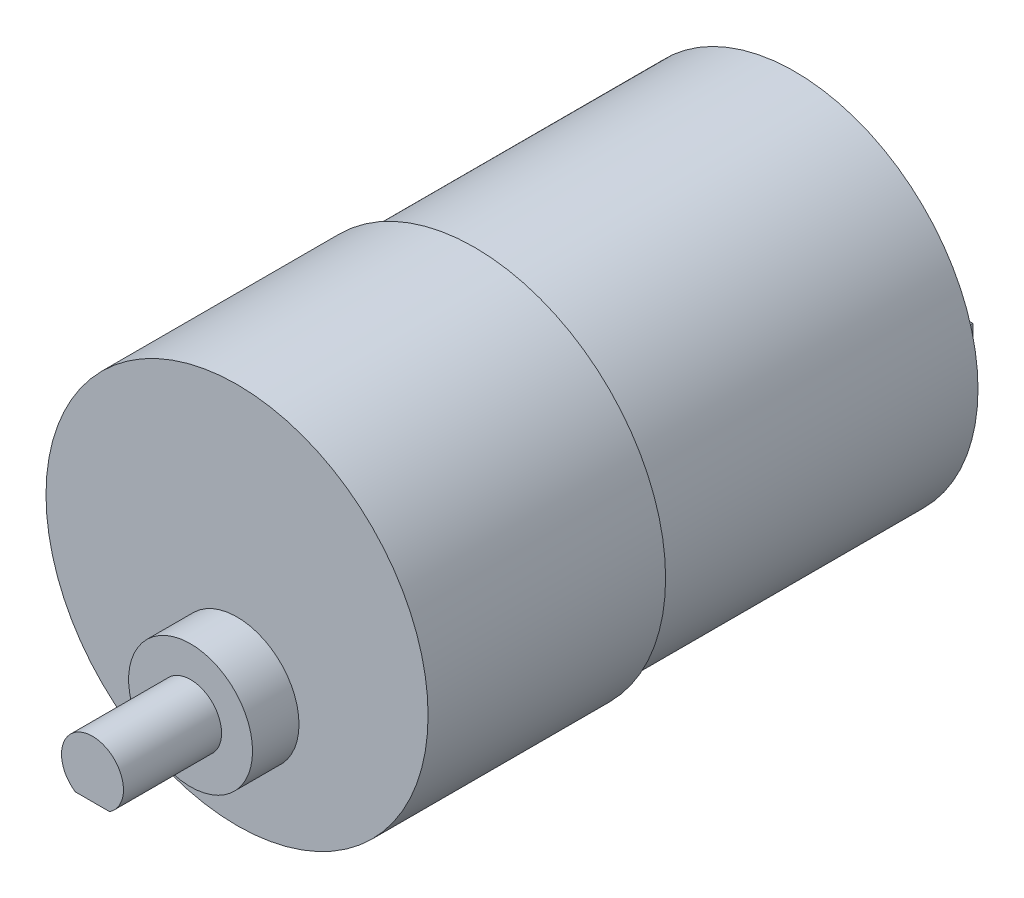
SolidWorks part; units mm, degrees
ref_plane "Front Plane" through (0, 0, 0) normal (0, 0, 1) x (1, 0, 0)
ref_plane "Top Plane" through (0, 0, 0) normal (0, 1, 0) x (1, 0, 0)
ref_plane "Right Plane" through (0, 0, 0) normal (1, 0, 0) x (0, 0, -1)
sketch "Sketch2" plane through (0, 0, 0) normal (0, 1, 0) x (1, 0, 0)
  line L0 (0, -54) -> (0, 0)
  line L1 (0, 0) -> (17.75, 0)
  line L2 (17.75, 0) -> (17.75, -31)
  line L3 (17.75, -31) -> (18.5, -31)
  line L4 (18.5, -31) -> (18.5, -54)
  line L5 (18.5, -54) -> (0, -54)
  point P3 (0, -2496.808)
  dimension "D1" = 17.75
  dimension "D2" = 18.5
  dimension "D3" = 31
  dimension "D4" = 23
revolve "Revolve1" add sketch "Sketch2" angle 360 about L0
sketch "Sketch3" plane through (0, 0, 0) normal (0, 0, -1) x (-1, 0, 0)
  line L0 (-12.5, 0) -> (0, 0) construction
  line L1 (-13.25, -1.25) -> (-11.75, -1.25)
  line L2 (-13.25, -1.25) -> (-13.25, 1.25)
  line L3 (-13.25, 1.25) -> (-11.75, 1.25)
  line L4 (-11.75, -1.25) -> (-11.75, 1.25)
  line L5 (-13.25, -1.25) -> (-11.75, 1.25) construction
  line L6 (-13.25, 1.25) -> (-11.75, -1.25) construction
  line L7 (11.75, -1.25) -> (13.25, -1.25)
  line L8 (11.75, -1.25) -> (11.75, 1.25)
  line L9 (11.75, 1.25) -> (13.25, 1.25)
  line L10 (13.25, -1.25) -> (13.25, 1.25)
  line L11 (11.75, -1.25) -> (13.25, 1.25) construction
  line L12 (11.75, 1.25) -> (13.25, -1.25) construction
  line L13 (0, 0) -> (12.5, 0) construction
  point P0 (-12.5, 0)
  point P5 (12.5, 0)
  dimension "D1" = 1.5
  dimension "D2" = 2.5
  dimension "D3" = 12.5
extrude "Boss-Extrude1" add sketch "Sketch3" along normal blind 4
sketch "Sketch4" plane through (0, 0, 54) normal (0, 0, 1) x (1, 0, 0)
  line L0 (-1.6583, -9.5) -> (1.6583, -9.5)
  circle A0 centre (0, -7) radius 6
  circle A1 centre (0, 0) radius 18.5 construction
  arc A2 (1.6583, -9.5) -> (-1.6583, -9.5) centre (0, -7) ccw
  dimension "D1" = 12
  dimension "D2" = 7
  dimension "D3" = 3
  dimension "D4" = 2.5
extrude "Boss-Extrude2" add sketch "Sketch4" along normal blind 4.5
extrude "Boss-Extrude3" add sketch "Sketch4<2>" along normal blind 14 contours L0 A2 region at (0, -6.888, 54)
sketch "Sketch4<2>" plane through (0, 0, 54) normal (0, 0, 1) x (1, 0, 0) same geometry as "Sketch4"
